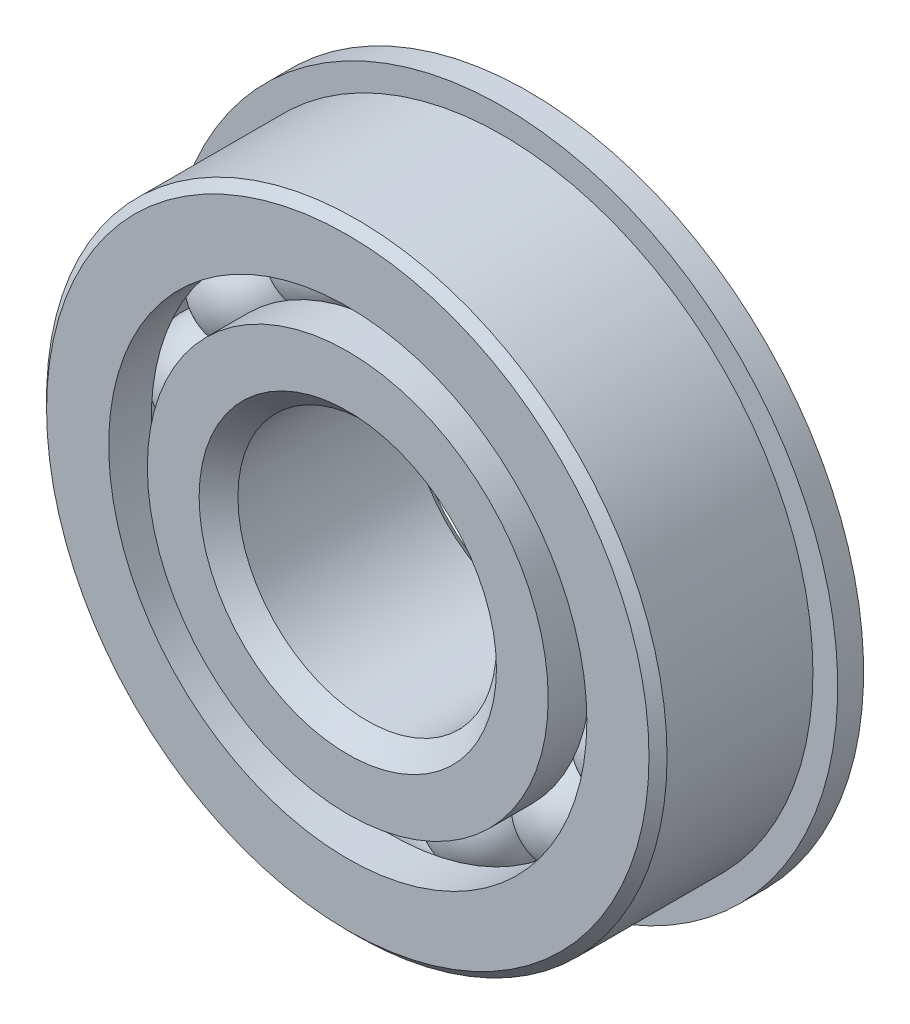
SolidWorks part; units mm, degrees
ref_plane "Front Plane" through (0, 0, 0) normal (0, 0, 1) x (1, 0, 0)
ref_plane "Top Plane" through (0, 0, 0) normal (0, 1, 0) x (1, 0, 0)
ref_plane "Right Plane" through (0, 0, 0) normal (1, 0, 0) x (0, 0, -1)
sketch "Sketch1" plane through (0, 0, 0) normal (1, 0, 0) x (0, 0, -1)
  line L0 (-5.5499, 0) -> (5.5499, 0) construction
  line L1 (0, 19.05) -> (0, -19.05) construction
  line L2 (4.9949, 19.05) -> (-4.9949, 19.05)
  line L3 (-4.9949, 19.05) -> (-5.5499, 18.495)
  line L4 (-5.5499, 18.495) -> (-5.5499, 14.6806)
  line L5 (-5.5499, 14.6806) -> (-2.9448, 14.6806)
  line L6 (5.5499, 14.6806) -> (2.9448, 14.6806)
  line L7 (5.5499, 18.495) -> (5.5499, 14.6806)
  line L8 (4.9949, 19.05) -> (5.5499, 18.495)
  line L9 (0, 19.05) -> (0, 13.4938) construction
  line L11 (5.5499, 0) -> (6.7532, 0) construction
  arc A0 (-2.9448, 14.6806) -> (2.9448, 14.6806) centre (0, 13.4938) cw
  circle A1 centre (0, 13.4938) radius 3.175 construction
  point P14 (0, 7.9375)
  dimension "D3" = 6.35
  dimension "D1" = 45
  dimension "Width" = 11.0998
  dimension "OD" = 38.1
  dimension "D2" = 0.555
  dimension "Shaft Dia" = 15.875
  dimension "D4" = 1.1868
  dimension "D5" = 5.5562
  dimension "Total Wd" = 12.3031
revolve "Revolve1" add sketch "Sketch1" angle 360 about L0
sketch "Sketch2" plane through (0, 0, 0) normal (1, 0, 0) x (0, 0, -1)
  line L0 (-5.5499, 12.3069) -> (-2.9448, 12.3069)
  line L1 (-5.5499, 18.495) -> (-5.5499, -18.495) construction
  line L2 (-5.5499, 12.3069) -> (-5.5499, 10.7175)
  line L3 (-5.5499, 10.7175) -> (-3.9605, 9.1281)
  line L4 (-3.9605, 9.1281) -> (0, 9.1281)
  line L5 (0, 19.05) -> (0, -19.05) construction
  line L6 (0, 9.1281) -> (0, 10.3188)
  line L7 (0, 10.3188) -> (0, 7.9375) construction
  line L8 (-5.5499, 12.3069) -> (-5.5499, 9.1281) construction
  line L9 (-5.5499, 9.1281) -> (-3.9605, 9.1281) construction
  arc A0 (-2.9448, 12.3069) -> (0, 10.3188) centre (0, 13.4938) ccw
  arc A1 (2.9448, 14.6806) -> (-2.9448, 14.6806) centre (0, 13.4938) ccw construction
  circle A2 centre (0, 13.4938) radius 3.175 construction
  dimension "D1" = 45
revolve "Revolve2" add sketch "Sketch2" angle 360 about L0
sketch "Sketch3" plane through (0, 0, 0) normal (1, 0, 0) x (0, 0, -1)
  line L0 (-5.5499, 10.7175) -> (-3.9605, 9.1281)
  line L1 (-3.9605, 9.1281) -> (0, 9.1281)
  line L2 (0, 9.1281) -> (0, 10.3188)
  line L3 (-5.5499, 10.7175) -> (-5.5499, 9.1281)
  line L4 (-5.5499, 12.3069) -> (-5.5499, 9.1281) construction
  line L5 (-5.5499, 9.1281) -> (-4.3593, 7.9375)
  line L6 (-4.3593, 7.9375) -> (6.1982, 7.9375)
  line L8 (6.1982, 7.9375) -> (6.7532, 8.4925)
  line L10 (6.7532, 8.4925) -> (6.7532, 12.3069)
  line L11 (6.7532, 12.3069) -> (2.9448, 12.3069)
  line L13 (4.9949, 19.05) -> (5.5499, 18.495) construction
  circle A0 centre (0, 13.4938) radius 3.175 construction
  arc A1 (2.9448, 12.3069) -> (0, 10.3188) centre (0, 13.4938) cw
revolve "Revolve3" add sketch "Sketch3" angle 360 about L0
sketch "Sketch4" plane through (0, 0, 0) normal (1, 0, 0) x (0, 0, -1)
  line L0 (-3.175, 13.4938) -> (3.175, 13.4938)
  circle A1 centre (0, 13.4938) radius 3.175 construction
  arc A2 (-3.175, 13.4938) -> (3.175, 13.4938) centre (0, 13.4938) cw
  arc A3 (2.9448, 14.6806) -> (-2.9448, 14.6806) centre (0, 13.4938) ccw construction
revolve "Revolve4" add sketch "Sketch4" angle 360 about L0
ref_axis "Axis1" through (0, 0, -5.5499) along (0, 0, 1)
pattern_circular "CirPattern1" count 13 every 27.692 about axis through (0, 0, -5.5499) along (0, 0, 1) of bodies 104
sketch "Sketch5" plane through (0, 0, 0) normal (1, 0, 0) x (0, 0, -1)
  line L0 (5.5499, 18.495) -> (5.5499, 14.6806) construction
  line L1 (5.5499, 16.5878) -> (3.9624, 16.5878)
  line L2 (5.5499, 16.5878) -> (5.5499, 20.574)
  line L3 (5.5499, 20.574) -> (3.9624, 20.574)
  line L4 (3.9624, 16.5878) -> (3.9624, 20.574)
  line L5 (6.7532, 0) -> (-5.5499, 0) construction
  dimension "Flange Thickness" = 1.5875
  dimension "Flange OD" = 41.148
revolve "Revolve5" add sketch "Sketch5" angle 360 about L5
equation "\"D2@Sketch1\" = \"Width@Sketch1\"*.05"
equation "\"D4@Sketch1\" = (((\"OD@Sketch1\"-\"Width@Sketch1\")/2)/3.25)/3.5"
equation "\"D2@CirPattern1\" = 360/\"Balls@CirPattern1\""
equation "\"D5@Sketch1\" = \"D3@Sketch1\" * 7/8"
